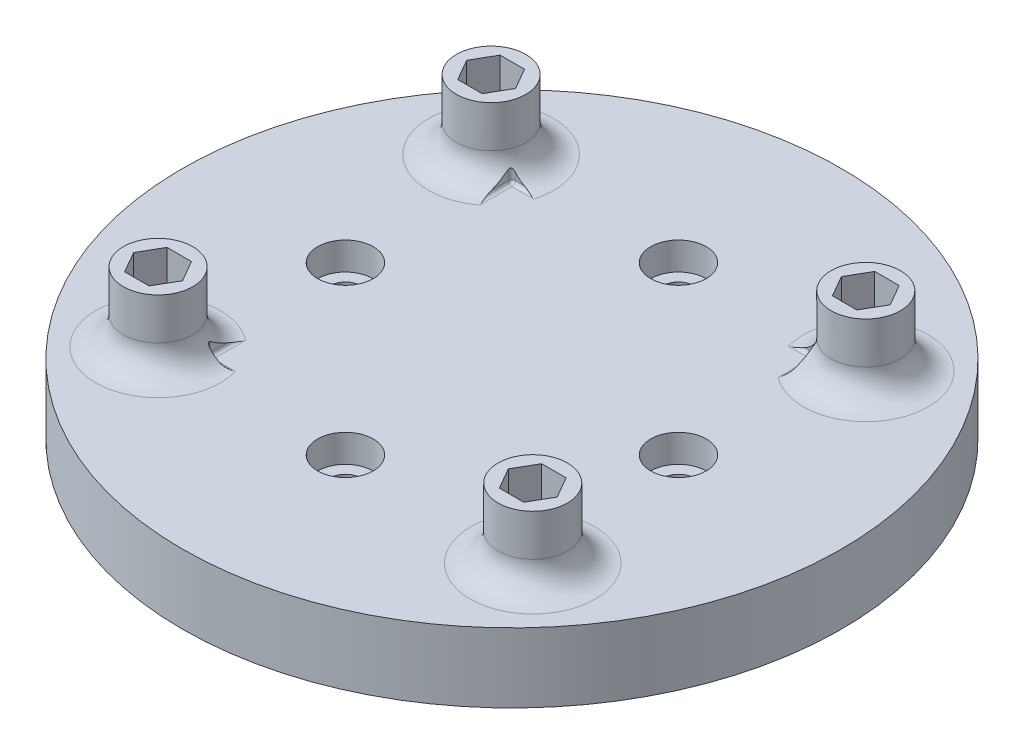
SolidWorks part; units mm, degrees
material "Nylon 101"
ref_plane "Front Plane" through (0, 0, 0) normal (0, 0, 1) x (1, 0, 0)
ref_plane "Top Plane" through (0, 0, 0) normal (0, 1, 0) x (1, 0, 0)
ref_plane "Right Plane" through (0, 0, 0) normal (1, 0, 0) x (0, 0, -1)
sketch "Sketch1" plane through (0, 0, 0) normal (0, 1, 0) x (1, 0, 0)
  circle A0 centre (0, 0) radius 47.5
  dimension "D1" = 95
extrude "Boss-Extrude1" add sketch "Sketch1" along normal blind 10
ref_plane "Plane1" through (0, 10, 0) normal (0, 1, 0) x (1, 0, 0)
sketch "Sketch2" plane through (0, 10, 0) normal (0, 1, 0) x (1, 0, 0)
  circle A0 centre (0, 0) radius 24 construction
  point P6 (0, 24)
  point P7 (-24, 0)
  point P14 (0, -24)
  point P15 (24, 0)
  dimension "D1" = 48
ref_plane "Plane2" through (0, 10, 0) normal (0, 1, 0) x (1, 0, 0)
sketch "Sketch3" plane through (0, 10, 0) normal (0, 1, 0) x (1, 0, 0)
  line L1 (-27, 24) -> (27, 24) construction
  line L2 (-27, 24) -> (-27, -24) construction
  line L3 (-27, -24) -> (27, -24) construction
  line L4 (27, 24) -> (27, -24) construction
  line L5 (-27, 24) -> (27, -24) construction
  line L6 (-27, -24) -> (27, 24) construction
  point P0 (0, 0)
  point P11 (-27, -24)
  point P12 (27, -24)
  point P13 (27, 24)
  point P14 (-27, 24)
  dimension "D1" = 54
  dimension "D2" = 48
hole_wizard "CBORE for M4 SBHCS1" positions "Sketch6" profile "Sketch7" counterbore size "M4" standard "ANSI Metric" end condition up to next
sketch "Sketch6" plane through (0, 0, 0) normal (0, -1, 0) x (-1, 0, 0)
  point P0 (27, -24)
  point P3 (-27, -24)
  point P6 (-27, 24)
  point P9 (27, 24)
sketch "Sketch7" plane through (-27, 0, 24) normal (1, 0, 0) x (0, 0, -1)
  line L0 (0, 0) -> (0, 10)
  line L1 (0, 10) -> (2.25, 10)
  line L3 (2.25, 10) -> (2.25, 2.3)
  line L4 (2.25, 2.3) -> (4.3, 2.3)
  line L5 (4.3, 2.3) -> (4.3, 0)
  line L7 (4.3, 0) -> (0, 0)
  line L11 (0, -6.35) -> (0, 107.95) construction
  dimension "Thru Hole Dia." = 4.5
  dimension "Thru Hole Depth" = 10
  dimension "C'Bore Dia." = 8.6
  dimension "C'Bore Depth" = 2.3
hole_wizard "CBORE for M4 SHCS1" positions "Sketch8" profile "Sketch9" counterbore size "M4" standard "ANSI Metric" end condition up to next
sketch "Sketch8" plane through (0, 10, 0) normal (0, 1, 0) x (1, 0, 0)
  point P0 (0, 24)
  point P3 (-24, 0)
  point P6 (24, 0)
  point P9 (0, -24)
sketch "Sketch9" plane through (0, 10, -24) normal (1, 0, 0) x (0, 0, 1)
  line L0 (0, 0) -> (0, 10)
  line L1 (0, 10) -> (2.25, 10)
  line L3 (2.25, 10) -> (2.25, 4)
  line L4 (2.25, 4) -> (4, 4)
  line L5 (4, 4) -> (4, 0)
  line L7 (4, 0) -> (0, 0)
  line L11 (0, -6.35) -> (0, 107.95) construction
  dimension "Thru Hole Dia." = 4.5
  dimension "Thru Hole Depth" = 10
  dimension "C'Bore Dia." = 8
  dimension "C'Bore Depth" = 4
sketch "Sketch10" plane through (0, 10, 0) normal (0, 1, 0) x (1, 0, 0)
  line L1 (-23.4782, -24) -> (-25.2391, -20.95)
  line L2 (-25.2391, -20.95) -> (-28.7609, -20.95)
  line L3 (-28.7609, -20.95) -> (-30.5218, -24)
  line L4 (-30.5218, -24) -> (-28.7609, -27.05)
  line L5 (-28.7609, -27.05) -> (-25.2391, -27.05)
  line L6 (-25.2391, -27.05) -> (-23.4782, -24)
  circle A0 centre (-27, -24) radius 3.05 construction
  circle A1 centre (-27, -24) radius 5
  dimension "D2" = 10
  dimension "D1" = 6.1
extrude "Boss-Extrude3" add sketch "Sketch10" along normal blind 10
mirror "Mirror1" about plane through (0, 0, 0) normal (0, 0, 1) of "Boss-Extrude3"
mirror "Mirror2" about plane through (0, 0, 0) normal (1, 0, 0) of "Mirror1"
fillet "Fillet1" radius 4 4 edges at (27, 10, -29) (27, 10, 29) (-27, 10, 29) (-27, 10, -19)
ref_plane "Plane3" through (0, 15, 0) normal (0, 1, 0) x (1, 0, 0)
sketch "Sketch13" plane through (0, 15, 0) normal (0, 1, 0) x (1, 0, 0)
  line L1 (-22, -22) -> (22, -22)
  line L2 (-22, -22) -> (-22, 22)
  line L3 (-22, 22) -> (22, 22)
  line L4 (22, -22) -> (22, 22)
  line L5 (-22, -22) -> (22, 22) construction
  line L6 (-22, 22) -> (22, -22) construction
  point P0 (0, 0)
  dimension "D1" = 44
  dimension "D2" = 44
extrude "Cut-Extrude1" cut sketch "Sketch13" against normal up to surface (5 mm away) up to face at (27, 10, -15)
fillet "Fillet2" radius 0.5 12 edges at (-22, 11.1437, -22) (-20.1125, 10, -22) (-22, 10, -19.2583) (-20.1125, 10, 22) (-22, 11.1437, 22) (-22, 10, 19.2583) (20.1125, 10, 22) (22, 11.1437, 22) (22, 10, 19.2583) (22, 10, -19.2583) (22, 11.1437, -22) (20.1125, 10, -22)
